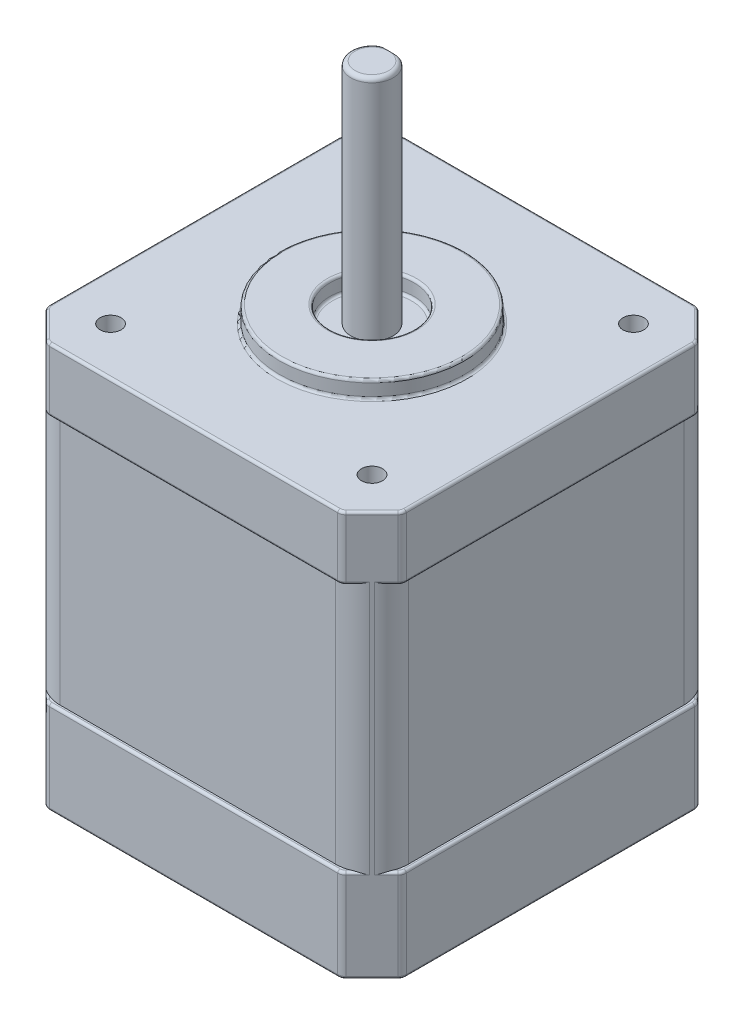
SolidWorks part; units mm, degrees
ref_plane "Front Plane" through (0, 0, 0) normal (0, 0, 1) x (1, 0, 0)
ref_plane "Top Plane" through (0, 0, 0) normal (0, 1, 0) x (1, 0, 0)
ref_plane "Right Plane" through (0, 0, 0) normal (1, 0, 0) x (0, 0, -1)
ref_plane "BottomMotorFacePlane" through (0, -48, 0) normal (0, 1, 0) x (1, 0, 0)
ref_plane "ProtrudngNubPlane" through (0, 2, 0) normal (0, 1, 0) x (1, 0, 0)
ref_plane "MotorShaftLimit" through (0, 27, 0) normal (0, 1, 0) x (1, 0, 0)
ref_plane "Front Cutout Plane" through (0, -7.5, 0) normal (0, 1, 0) x (1, 0, 0)
ref_plane "Rear Cutout Plane" through (0, -37, 0) normal (0, 1, 0) x (1, 0, 0)
ref_plane "JST Connnector Side Plane" through (-8, 0, 0) normal (1, 0, 0) x (0, 0, -1)
sketch "MasterLayoutSketch" plane through (0, 0, 0) normal (0, 1, 0) x (1, 0, 0)
  line L12 (-21.15, 21.15) -> (21.15, -21.15) construction
  line L13 (-21.15, 21.15) -> (21.15, 21.15) construction
  line L14 (-21.15, 21.15) -> (-21.15, -21.15) construction
  line L15 (-21.15, -21.15) -> (21.15, -21.15) construction
  line L17 (-21.15, -21.15) -> (21.15, 21.15) construction
  line L18 (21.15, 21.15) -> (21.15, -21.15) construction
  line L19 (-21.15, 17.5) -> (-21.15, -17.5)
  line L20 (-21.15, -17.5) -> (-17.5, -21.15)
  line L21 (-17.5, -21.15) -> (17.5, -21.15)
  line L22 (17.5, -21.15) -> (21.15, -17.5)
  line L23 (21.15, -17.5) -> (21.15, 17.5)
  line L24 (21.15, 17.5) -> (17.5, 21.15)
  line L25 (17.5, 21.15) -> (-17.5, 21.15)
  line L26 (-17.5, 21.15) -> (-21.15, 17.5)
  line L27 (-1.5, 2) -> (1.5, 2)
  line L28 (0, -2.5) -> (0, 2) construction
  circle A0 centre (0, 0) radius 11
  arc A1 (-1.5, 2) -> (1.5, 2) centre (0, 0) ccw
  point P8 (-15.5, 15.5)
  point P18 (15.5, 15.5)
  point P19 (15.5, -15.5)
  point P22 (-15.5, -15.5)
  dimension "D3" = 22
  dimension "D4" = 5
  dimension "D6" = 31
  dimension "D1" = 42.3
  dimension "D2" = 35
  dimension "D5" = 4.5
sketch "HolePositionSketch" plane through (0, 0, 0) normal (0, 1, 0) x (1, 0, 0)
  point P0 (-15.5, -15.5)
  point P2 (15.5, -15.5)
  point P4 (15.5, 15.5)
  point P6 (-15.5, 15.5)
sketch "MainBodySketch" plane through (0, 0, 0) normal (0, 1, 0) x (1, 0, 0)
  line L0 (21.15, 17.5) -> (17.5, 21.15) construction
  line L1 (21.15, -17.5) -> (21.15, 17.5) construction
  line L2 (17.5, -21.15) -> (21.15, -17.5) construction
  line L3 (-17.5, -21.15) -> (17.5, -21.15) construction
  line L4 (-21.15, -17.5) -> (-17.5, -21.15) construction
  line L5 (-21.15, 17.5) -> (-21.15, -17.5) construction
  line L6 (17.5, 21.15) -> (-17.5, 21.15) construction
  line L7 (-17.5, 21.15) -> (-21.15, 17.5) construction
  line L8 (21.15, 17.5) -> (17.5, 21.15)
  line L9 (21.15, -17.5) -> (21.15, 17.5)
  line L10 (17.5, -21.15) -> (21.15, -17.5)
  line L11 (-17.5, -21.15) -> (17.5, -21.15)
  line L12 (-21.15, -17.5) -> (-17.5, -21.15)
  line L13 (-21.15, 17.5) -> (-21.15, -17.5)
  line L14 (17.5, 21.15) -> (-17.5, 21.15)
  line L15 (-17.5, 21.15) -> (-21.15, 17.5)
extrude "MainMotorBody" add sketch "MainBodySketch" against normal up to surface (48 mm away) up to plane "BottomMotorFacePlane"
sketch "ProtrudingNubSketch" plane through (0, 0, 0) normal (0, 1, 0) x (1, 0, 0)
  circle A0 centre (0, 0) radius 11 construction
  circle A1 centre (0, 0) radius 11
  circle A2 centre (0, 0) radius 5
  dimension "D1" = 10
extrude "ProtrudingNub" add sketch "ProtrudingNubSketch" along normal up to surface (2 mm away) up to plane "ProtrudngNubPlane"
sketch "MotorShaftSketch" plane through (0, 0, 0) normal (0, 1, 0) x (1, 0, 0)
  line L0 (-1.5, 2) -> (1.5, 2) construction
  line L1 (-1.5, 2) -> (1.5, 2)
  arc A0 (-1.5, 2) -> (1.5, 2) centre (0, 0) ccw construction
  arc A1 (-1.5, 2) -> (1.5, 2) centre (0, 0) ccw
extrude "MotorShaft" add sketch "MotorShaftSketch" along normal up to surface (27 mm away) up to plane "MotorShaftLimit"
sketch "JST-PHConnectorSketch" plane through (0, -48, 0) normal (0, 1, 0) x (1, 0, 0)
  line L0 (17.5, 21.15) -> (-17.5, 21.15) construction
  line L1 (-8, 21.15) -> (8, 21.15)
  line L2 (-8, 21.15) -> (-8, 27.15)
  line L3 (-8, 27.15) -> (8, 27.15)
  line L4 (8, 21.15) -> (8, 27.15)
  line L5 (-8, 21.15) -> (8, 27.15) construction
  line L6 (-8, 27.15) -> (8, 21.15) construction
  point P0 (0, 24.15)
  dimension "D1" = 6
  dimension "D2" = 16
extrude "JST Connector" add sketch "JST-PHConnectorSketch" along normal blind 10.9
hole_wizard "M3MountingHoles" positions "Sketch8" profile "Sketch9" tap size "M3" standard "ISO"
sketch "Sketch8" plane through (0, 0, 0) normal (0, 1, 0) x (1, 0, 0)
  point P0 (-15.5, 15.5)
  point P3 (15.5, 15.5)
  point P6 (15.5, -15.5)
  point P9 (-15.5, -15.5)
sketch "Sketch9" plane through (-15.5, 0, -15.5) normal (1, 0, 0) x (0, 0, 1)
  line L0 (0, 0) -> (0, 6.7511)
  line L1 (0, 6.7511) -> (1.25, 6)
  line L2 (1.25, 6) -> (1.25, 0)
  line L5 (1.25, 0) -> (0, 0)
  line L10 (0, 6.7511) -> (-1.25, 6) construction
  line L11 (0, -6.35) -> (0, 107.95) construction
  dimension "Tap Drill Dia." = 2.5
  dimension "Tap Drill Depth" = 6
  dimension "Drill Angle" = 118
cosmetic thread "Hole Thread1" parameters "D1"=4.5, "D2"=3
cosmetic thread "Hole Thread2" parameters "D1"=4.5, "D2"=3
cosmetic thread "Hole Thread3" parameters "D1"=4.5, "D2"=3
cosmetic thread "Hole Thread4" parameters "D1"=4.5, "D2"=3
sketch "Cutout Sketch" plane through (0, -7.5, 0) normal (0, 1, 0) x (1, 0, 0)
  line L0 (21.15, 17.5) -> (17.5, 21.15) construction
  line L1 (17.5, 21.15) -> (-17.5, 21.15) construction
  line L2 (-17.5, 21.15) -> (-21.15, 17.5) construction
  line L3 (-21.15, 17.5) -> (-21.15, -17.5) construction
  line L4 (-21.15, -17.5) -> (-17.5, -21.15) construction
  line L5 (-17.5, -21.15) -> (17.5, -21.15) construction
  line L6 (17.5, -21.15) -> (21.15, -17.5) construction
  line L7 (21.15, -17.5) -> (21.15, 17.5) construction
  line L8 (21.15, 17.5) -> (20.65, 18)
  line L9 (17.5, 21.15) -> (-17.5, 21.15)
  line L10 (-17.5, 21.15) -> (-18, 20.65)
  line L11 (-21.15, 17.5) -> (-21.15, -17.5)
  line L12 (-21.15, -17.5) -> (-20.65, -18)
  line L13 (-17.5, -21.15) -> (17.5, -21.15)
  line L14 (17.5, -21.15) -> (18, -20.65)
  line L15 (21.15, -17.5) -> (21.15, 17.5)
  line L16 (-20.65, 18) -> (-20.65, -18)
  line L17 (-20.65, -20.65) -> (20.65, -20.65) construction
  line L18 (-20.65, -20.65) -> (-20.65, 20.65) construction
  line L19 (-20.65, 20.65) -> (20.65, 20.65) construction
  line L20 (20.65, -20.65) -> (20.65, 20.65) construction
  line L21 (-20.65, -20.65) -> (20.65, 20.65) construction
  line L22 (-20.65, 20.65) -> (20.65, -20.65) construction
  line L23 (-18, -20.65) -> (18, -20.65)
  line L24 (20.65, -18) -> (20.65, 18)
  line L25 (18, 20.65) -> (-18, 20.65)
  line L26 (-20.65, 18) -> (-21.15, 17.5)
  line L27 (18, 20.65) -> (17.5, 21.15)
  line L28 (20.65, -18) -> (21.15, -17.5)
  line L29 (-18, -20.65) -> (-17.5, -21.15)
  point P2 (0, 0)
  dimension "D1" = 0.5
extrude "Cutout" cut sketch "Cutout Sketch" against normal up to surface (29.5 mm away)
sketch "JST Connector Cutout" plane through (-8, 0, 0) normal (1, 0, 0) x (0, 0, -1)
  line L0 (27.15, -44) -> (21.15, -44)
  line L1 (21.15, -48) -> (27.15, -48) construction
  line L2 (21.15, -48) -> (27.15, -48) construction
  line L3 (21.15, -48) -> (21.15, -37) construction
  line L4 (21.15, -37) -> (27.15, -37) construction
  line L5 (27.15, -37) -> (27.15, -48) construction
  line L6 (21.15, -44) -> (21.15, -43.5)
  line L7 (21.15, -43.5) -> (27.15, -43.5)
  line L8 (27.15, -43.5) -> (27.15, -44)
  dimension "D1" = 11
  dimension "D2" = 0.5
  dimension "D3" = 4
extrude "JST Connector Split Cutout" cut sketch "JST Connector Cutout" along normal through all
fillet "Cosmetic Fillets" radius 4 8 edges at (18, -22.25, 20.65) (20.65, -22.25, 18) (-18, -22.25, 20.65) (-20.65, -22.25, 18) (-18, -22.25, -20.65) (-20.65, -22.25, -18) (18, -22.25, -20.65) (20.65, -22.25, -18)
fillet "Tiny Fillets" radius 1 16 edges at (-17.5, -3.75, -21.15) (-21.15, -3.75, -17.5) (-21.15, -3.75, 17.5) (-17.5, -3.75, 21.15) (17.5, -3.75, 21.15) (21.15, -3.75, 17.5) (21.15, -3.75, -17.5) (17.5, -3.75, -21.15) (17.5, -42.5, -21.15) (21.15, -42.5, -17.5) (21.15, -42.5, 17.5) (17.5, -42.5, 21.15) (-17.5, -42.5, 21.15) (-21.15, -42.5, 17.5) (-17.5, -42.5, -21.15) (-21.15, -42.5, -17.5)
fillet "Rear Block Fillets" radius 1 4 edges at (8, -46, -21.15) (-8, -46, -21.15) (8, -46, -27.15) (-8, -46, -27.15)
fillet "Nub Fillets" radius 0.3 4 edges at (0, 2, 11) (0, 0, 11) (0, 0, 5) (0, 2, 5)
fillet "Shaft Fillets" radius 0.5 3 edges at (0, 27, 2.5) (1.5, 13.5, -2) (-1.5, 13.5, -2)
fillet "Faceplate Fillets" radius 0.3 80 edges at (20.1678, -37, -18.4822) (21.0739, -37, -17.4685) (20.1678, -37, 18.4822) (21.0739, -37, 17.4685) (18.4822, -7.5, -20.1678) (17.4685, -7.5, -21.0739) (-18.4822, -7.5, -20.1678) (-17.4685, -7.5, -21.0739) (20.1678, -7.5, 18.4822) (21.0739, -7.5, 17.4685) (20.1678, -7.5, -18.4822) (21.0739, -7.5, -17.4685) (-18.4822, -7.5, 20.1678) (-17.4685, -7.5, 21.0739) (18.4822, -7.5, 20.1678) (17.4685, -7.5, 21.0739) (-20.1678, -7.5, -18.4822) (-21.0739, -7.5, -17.4685) (-20.1678, -7.5, 18.4822) (-21.0739, -7.5, 17.4685) (18.4822, -37, 20.1678) (17.4685, -37, 21.0739) (-18.4822, -37, 20.1678) (-17.4685, -37, 21.0739) (-20.1678, -37, 18.4822) (-21.0739, -37, 17.4685) (-20.1678, -37, -18.4822) (-21.0739, -37, -17.4685) (-18.4822, -37, -20.1678) (-17.4685, -37, -21.0739) (18.4822, -37, -20.1678) (17.4685, -37, -21.0739) (17.4685, 0, -21.0739) (19.325, 0, -19.325) (21.0739, 0, -17.4685) (21.15, 0, 0) (21.0739, 0, 17.4685) (19.325, 0, 19.325) (17.4685, 0, 21.0739) (0, 0, 21.15) (-17.4685, 0, 21.0739) (-19.325, 0, 19.325) (-21.0739, 0, 17.4685) (-21.15, 0, 0) (-21.0739, 0, -17.4685) (-19.325, 0, -19.325) (-17.4685, 0, -21.0739) (-17.4685, -48, -21.0739) (-19.325, -48, -19.325) (-21.0739, -48, -17.4685) (-21.15, -48, 0) (-21.0739, -48, 17.4685) (-19.325, -48, 19.325) (-17.4685, -48, 21.0739) (0, -48, 21.15) (17.4685, -48, 21.0739) (19.325, -48, 19.325) (21.0739, -48, 17.4685) (21.15, -48, 0) (21.0739, -48, -17.4685) (19.325, -48, -19.325) (17.4685, -48, -21.0739) (13.0429, -48, -21.15) (8.2929, -48, -21.4429) (8, -48, -24.15) (7.7071, -48, -26.8571) (0, -48, -27.15) (-7.7071, -48, -26.8571) (-8, -48, -24.15) (-8.2929, -48, -21.4429) (21.15, -37, 0) (0, -7.5, -21.15) (21.15, -7.5, 0) (0, -7.5, 21.15) (-21.15, -7.5, 0) (0, -37, 21.15) (-21.15, -37, 0) (0, -37, -21.15) (0, 0, -21.15) (-13.0429, -48, -21.15)
